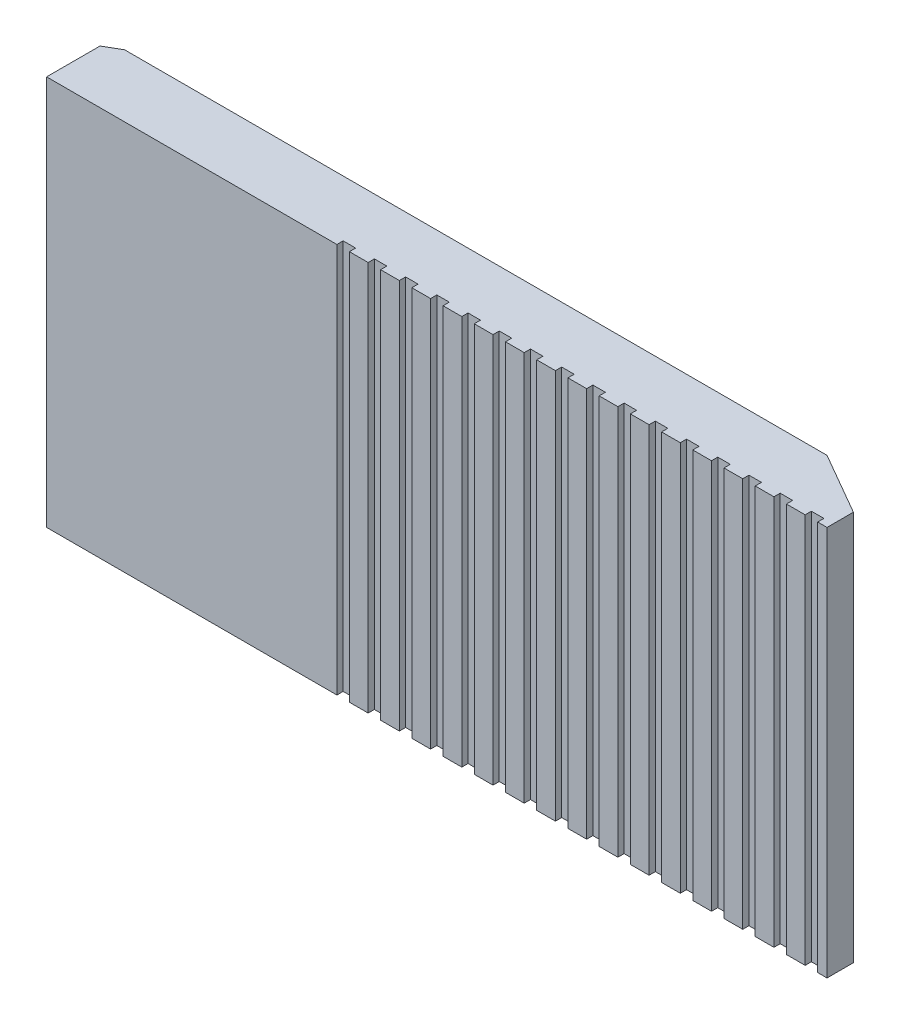
SolidWorks part; units mm, degrees
ref_plane "Płaszczyzna przednia" through (0, 0, 0) normal (0, 0, 1) x (1, 0, 0)
ref_plane "Płaszczyzna górna" through (0, 0, 0) normal (0, 1, 0) x (1, 0, 0)
ref_plane "Płaszczyzna prawa" through (0, 0, 0) normal (1, 0, 0) x (0, 0, -1)
sketch "Szkic1" plane through (0, 0, 0) normal (0, 0, 1) x (1, 0, 0)
  line L1 (-25, 12.5) -> (25, 12.5)
  line L2 (-25, 12.5) -> (-25, -12.5)
  line L3 (-25, -12.5) -> (25, -12.5)
  line L4 (25, 12.5) -> (25, -12.5)
  line L5 (-25, 12.5) -> (0, 0) construction
  line L6 (-25, -12.5) -> (0, 0) construction
  point P0 (0, 0)
  point P6 (9, 0)
  dimension "D1" = 50
  dimension "D4" = 0
  dimension "D5" = 25
  dimension "D6" = 16
extrude "Dodanie-wyciągnięcie1" add sketch "Szkic1" along normal blind 4
chamfer "Sfazowanie1" distance 4 angle 30 1 edges at (25, 0, 0) first distance on face at (0, 0, 0)
sketch "Szkic2" plane through (0, 0, 0) normal (0, 0, -1) x (-1, 0, 0)
  line L0 (-25, -12.5) -> (-25, 12.5) construction
  line L1 (-15, 5) -> (-5, 5)
  line L2 (-15, 5) -> (-15, -5)
  line L3 (-15, -5) -> (-5, -5)
  line L4 (-5, 5) -> (-5, -5)
  line L5 (-15, 5) -> (-5, -5) construction
  line L6 (-15, -5) -> (-5, 5) construction
  point P0 (-10, 0)
  point P5 (-25, 0)
  dimension "D1" = 10
  dimension "D2" = 10
  dimension "D3" = 0
  dimension "D4" = 15
extrude "Dodanie-wyciągnięcie2" add sketch "Szkic2" along normal blind 5.5
sketch "Szkic3" plane through (0, 12.5, 0) normal (0, 1, 0) x (1, 0, 0)
  line L0 (25, -4) -> (-25, -4) construction
  line L1 (23.6, -4.4) -> (24.4, -4.4)
  line L2 (23.6, -4.4) -> (23.6, -3.6)
  line L3 (23.6, -3.6) -> (24.4, -3.6)
  line L4 (24.4, -4.4) -> (24.4, -3.6)
  line L5 (23.6, -4.4) -> (24.4, -3.6) construction
  line L6 (23.6, -3.6) -> (24.4, -4.4) construction
  point P0 (24, -4)
  dimension "D1" = 0.8
  dimension "D2" = 0.8
  dimension "D3" = 1
extrude "Wytnij-wyciągnięcie1" cut sketch "Szkic3" against normal up to next
pattern_linear "Szyk liniowy1" count 16 spacing 2 along (-1, 0, 0) of "Wytnij-wyciągnięcie1"
chamfer "Sfazowanie2" distance 1 angle 30 1 edges at (-25, 0, 0) first distance on face at (-2, 0, 0)
